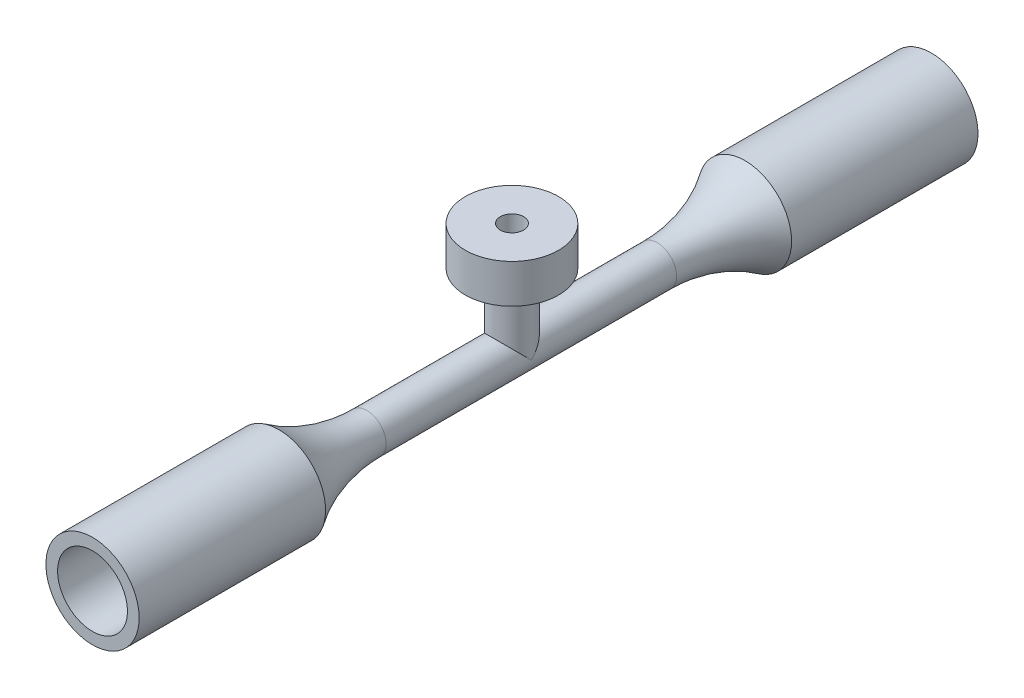
SolidWorks part; units mm, degrees
ref_plane "Front Plane" through (0, 0, 0) normal (0, 0, 1) x (1, 0, 0)
ref_plane "Top Plane" through (0, 0, 0) normal (0, 1, 0) x (1, 0, 0)
ref_plane "Right Plane" through (0, 0, 0) normal (1, 0, 0) x (0, 0, -1)
sketch "Sketch1" plane through (0, 0, 0) normal (0, 0, 1) x (1, 0, 0)
  circle A0 centre (0, 0) radius 3
  dimension "D1" = 6
extrude "Boss-Extrude1" add sketch "Sketch1" along normal blind 12
sketch "Sketch2" plane through (0, 0, 12) normal (0, 0, 1) x (1, 0, 0)
  circle A0 centre (0, 0) radius 1.25
  dimension "D1" = 2.5
extrude "Boss-Extrude2" add sketch "Sketch2" along normal blind 15
sketch "Sketch3" plane through (0, 0, 0) normal (0, 1, 0) x (1, 0, 0)
  line L0 (-1.25, -27) -> (1.25, -27)
  arc A0 (1.25, -27) -> (-1.25, -27) centre (0, -27) ccw
extrude "Boss-Extrude3" add sketch "Sketch3" along normal blind 4.5
sketch "Sketch4" plane through (0, 4.5, 0) normal (0, 1, 0) x (1, 0, 0)
  line L0 (-1.25, -27) -> (1.25, -27) construction
  line L1 (-3, -27) -> (3, -27)
  arc A0 (3, -27) -> (-3, -27) centre (0, -27) ccw
  dimension "D1" = 6
extrude "Boss-Extrude4" add sketch "Sketch4" along normal blind 2.5
sketch "Sketch5" plane through (0, 0, 0) normal (0, 0, -1) x (-1, 0, 0)
  circle A0 centre (0, 0) radius 2.25
  dimension "D1" = 4.5
extrude "Cut-Extrude1" cut sketch "Sketch5" against normal blind 10.5
sketch "Sketch6" plane through (0, 0, 27) normal (0, 0, 1) x (1, 0, 0)
  circle A0 centre (0, 0) radius 0.75
  dimension "D1" = 1.5
extrude "Cut-Extrude2" cut sketch "Sketch6" against normal blind 21.5
sketch "Sketch7" plane through (0, 7, 0) normal (0, 1, 0) x (1, 0, 0)
  line L0 (-0.75, -27) -> (-0.75, -27.0555)
  line L3 (-0.75, -27.0555) -> (0.75, -27.0555)
  line L4 (0.75, -27.0555) -> (0.75, -27)
  arc A0 (-0.75, -27) -> (0.75, -27) centre (0, -27) cw
  point P4 (0, -27.0555)
  dimension "D1" = 0.75
  dimension "D2" = 1.5
  dimension "D3" = 0.0555
  dimension "D4" = 27
extrude "Cut-Extrude3" cut sketch "Sketch7" against normal blind 7
fillet "Fillet1" radius 10 1 edges at (1.25, 0, 12)
ref_plane "Plane2" through (0, 0, 27) normal (0, 0, 1) x (1, 0, 0)
mirror "Mirror5" about plane through (0, 0, 27) normal (0, 0, 1) of bodies 107
